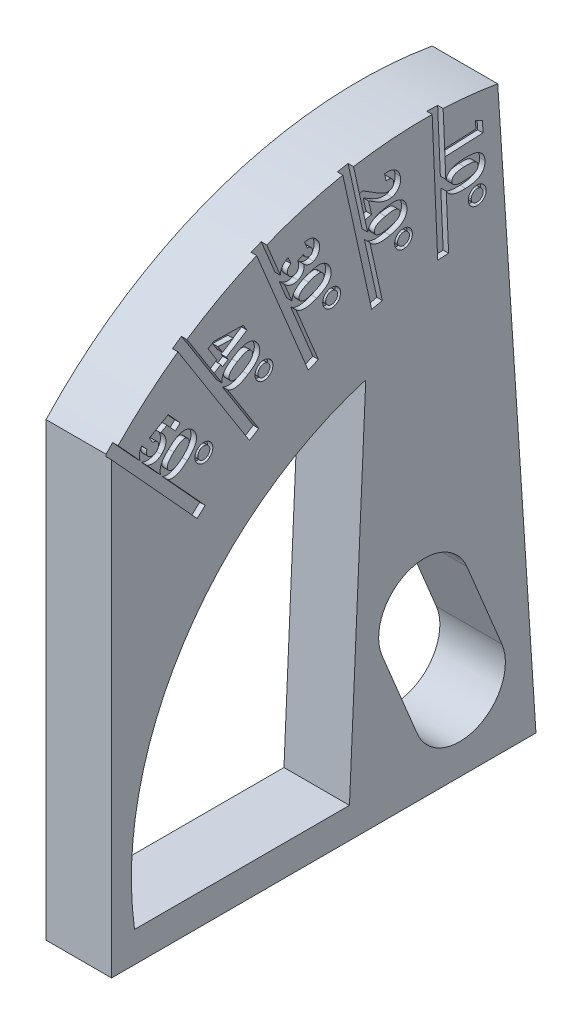
SolidWorks part; units mm, degrees
ref_plane "Front Plane" through (0, 0, 0) normal (0, 0, 1) x (1, 0, 0)
ref_plane "Top Plane" through (0, 0, 0) normal (0, 1, 0) x (1, 0, 0)
ref_plane "Right Plane" through (0, 0, 0) normal (1, 0, 0) x (0, 0, -1)
sketch "Sketch2" plane through (0, 0, 0) normal (1, 0, 0) x (0, 0, -1)
  line L0 (-8.5, 42.0279) -> (-7, 7) construction
  line L1 (0, 0) -> (-14, 0)
  line L5 (-7, 7) -> (-22.9981, 6.3149) construction
  line L6 (-14.5597, 41.2353) -> (-7, 7) construction
  line L7 (-20.3898, 39.4024) -> (-7, 7) construction
  line L8 (0, 0) -> (-3.5, 53.243)
  line L9 (-25.813, 36.585) -> (-7, 7) construction
  line L10 (-30.6646, 32.8687) -> (-7, 7) construction
  line L11 (-13.233, 49.161) -> (-10.0249, 41.3977)
  line L12 (-14, 0) -> (-38.8726, 0)
  line L13 (-38.8726, 0) -> (-38.8726, 41.2968)
  line L14 (-6.9751, 42.658) -> (-10.1831, 50.4213)
  line L15 (-14.0897, 13.1592) -> (-10.8816, 5.396)
  line L16 (-6.3264, 16.3673) -> (-3.1184, 8.604)
  line L17 (-32.1895, 32.2386) -> (-35.3975, 40.0019)
  line L18 (-29.1396, 33.4989) -> (-32.3477, 41.2622)
  line L19 (-17.208, 0) -> (-14.7869, 53.554) construction
  line L20 (-38.8726, 2.8) -> (-17.0815, 2.8)
  line L21 (-30.546, 43.7182) -> (-27.3379, 35.9549)
  line L22 (-27.4961, 44.9785) -> (-24.2881, 37.2152)
  line L23 (-25.1228, 46.5355) -> (-21.9147, 38.7723)
  line L24 (-22.0729, 47.7959) -> (-18.8649, 40.0326)
  line L25 (-19.2927, 48.3684) -> (-16.0847, 40.6051)
  line L26 (-16.2429, 49.6287) -> (-13.0348, 41.8654)
  line L27 (-17.0815, 2.8) -> (-15.5893, 35.8067)
  circle A0 centre (-7, 7) radius 4.2
  circle A2 centre (-8.5, 42.0279) radius 1.65
  circle A3 centre (-7, 7) radius 35.06 construction
  circle A4 centre (-14.5597, 41.2353) radius 1.65
  circle A5 centre (-7, 7) radius 30.06
  circle A6 centre (-7, 7) radius 40.06 construction
  circle A7 centre (-20.3898, 39.4024) radius 1.65
  circle A8 centre (-25.813, 36.585) radius 1.65
  circle A9 centre (-30.6646, 32.8687) radius 1.65
  circle A11 centre (-10.208, 14.7633) radius 4.2
  circle A12 centre (-10.208, 14.7633) radius 35.06 construction
  circle A13 centre (-33.8726, 40.632) radius 1.65
  circle A14 centre (-11.708, 49.7912) radius 1.65
  circle A15 centre (-10.208, 14.7633) radius 36.71
  circle A16 centre (-10.208, 14.7633) radius 33.41
  circle A17 centre (-10.208, 14.7633) radius 39.06
  circle A18 centre (-29.021, 44.3483) radius 1.65
  circle A19 centre (-23.5978, 47.1657) radius 1.65
  circle A20 centre (-17.7678, 48.9985) radius 1.65
  point P7 (-7, 0)
  point P72 (0, 0)
  point P74 (0, 0)
  dimension "D3" = 8.4
  dimension "D5" = 3.3
  dimension "D6" = 70.12
  dimension "D8" = 10
  dimension "D11" = 5
  dimension "D12" = 10
  dimension "D13" = 10
  dimension "D14" = 4
  dimension "D17" = 70.12
  dimension "D15" = 3.0789
  dimension "D18" = 5
  dimension "D19" = 3.3
  dimension "D1" = 5
  dimension "D2" = 7
  dimension "D4" = 7
  dimension "D7" = 1.5
  dimension "D9" = 10
  dimension "D16" = 7
  dimension "D10" = 5
extrude "Boss-Extrude6" add sketch "Sketch2" along normal blind 3 contours L8 A5 L27 L20 L12 L1 A11 L16 A0 L15 | A5 L20 L13 L12 | L8 A17 L13 L20 A5 A20 L26 A4 L25 A19 L24 A7 L23 A18 L22 A8 L21 A13 L18 A9 L17 A14 L14 A2 L11 | A13 | A13 L17 A9 L18 | A9 | A8 | A7 | A4 | A2 | A14 L11 A2 L14 | A20 L25 A4 L26 | A19 L23 A7 L24 | A18 L21 A8 L22 | A18 | A19 | L8 A17 L13 A15 | A16 L17 A13 A15 L13 | A16 A13 L17 | A16 L18 A13 | A18 A15 A13 L18 A16 L21 | A18 L21 A16 | A18 A16 L22 | A19 A15 A18 L22 A16 L23 | A19 L23 A16 | A19 A16 L24 | A20 A15 A19 L24 A16 L25 | A20 L25 A16 | A16 L8 A15 A14 L14 | A16 L14 A14 | A20 L26 A16 L11 A14 A15 | A20 A16 L26 | A16 A14 L11 | A20 | A14 region at (0, 0.522, 7) region at (0, 33.001, 24.3817) region at (0, 1.3473, 37.6924) region at (0, 49.6423, 6.6257) region at (0, 51.7655, 7.5138) region at (0, 48.7084, 10.044) region at (0, 45.6614, 10.0725) region at (0, 37.0768, 37.033) region at (0, 49.7013, 14.6927) region at (0, 42.0279, 8.5) region at (0, 48.3248, 12.6352) region at (0, 36.5524, 32.1158) region at (0, 38.6904, 34.2868) region at (0, 48.3604, 20.7414) region at (0, 48.9985, 17.7678) region at (0, 42.6753, 31.6952) region at (0, 40.632, 33.8726) region at (0, 32.8687, 30.6646) region at (0, 40.2479, 32.1808) region at (0, 45.9955, 26.4644) region at (0, 47.1657, 23.5978) region at (0, 48.1126, 16.0991) region at (0, 47.4238, 18.5791) region at (0, 44.9135, 16.1134) region at (0, 44.3483, 29.021) region at (0, 46.4572, 21.9203) region at (0, 45.4796, 24.2859) region at (0, 41.2353, 14.5597) region at (0, 43.8056, 27.3347) region at (0, 42.5429, 29.5775) region at (0, 40.2871, 27.3091) region at (0, 43.1027, 21.9188) region at (0, 36.585, 25.813) region at (0, 39.4024, 20.3898)
extrude "Boss-Extrude7" add sketch "Sketch2<12>" against normal blind 3 contours L8 A17 L13 A15 | A16 L8 A15 A14 L14 | L8 A16 L14 A2 L11 L26 A4 L25 L24 A7 L23 L22 A8 L21 L18 A9 L17 L13 L20 A5 | L8 A5 L27 L20 L12 L1 A11 L16 A0 L15 | A5 L20 L13 L12 | A16 L17 A13 A15 L13 region at (0, 0.522, 7) region at (0, 33.001, 24.3817) region at (0, 1.3473, 37.6924) region at (0, 49.6423, 6.6257) region at (0, 51.7655, 7.5138) region at (0, 37.0768, 37.033)
sketch "Sketch2<12>" plane through (0, 0, 0) normal (1, 0, 0) x (0, 0, -1) same geometry as "Sketch2"
sketch "Sketch5" plane through (3, 0, 0) normal (1, 0, 0) x (0, 0, -1)
  line L0 (-8.5, 42.0279) -> (-9.0501, 54.8734)
  line L1 (-14.5597, 41.2353) -> (-17.4386, 54.2724)
  line L2 (-20.3898, 39.4024) -> (-25.5288, 51.8384)
  line L3 (-25.813, 36.585) -> (-33.6355, 48.8866)
  line L4 (-30.6646, 32.8687) -> (-40.0326, 43.1093)
  line L5 (-30.6646, 32.8687) -> (-7, 7) construction
  line L6 (-7, 7) -> (-25.813, 36.585) construction
  line L7 (-20.3898, 39.4024) -> (-7, 7) construction
  line L8 (-7, 7) -> (-14.5597, 41.2353) construction
  line L9 (-7, 7) -> (-8.5, 42.0279) construction
  circle A0 centre (-7, 7) radius 35.06 construction
  circle A1 centre (-7, 7) radius 35.06 construction
  point P0 (-30.6646, 32.8687)
  point P2 (-25.813, 36.585)
  point P4 (-20.3898, 39.4024)
  point P6 (-14.5597, 41.2353)
  point P8 (-8.5, 42.0279)
  point P15 (-9.0501, 54.8734)
  point P16 (-17.4386, 54.2724)
  point P17 (-25.5288, 51.8384)
  point P26 (-33.6355, 48.8866)
  point P27 (-40.0326, 43.1093)
extrude "Cut-Extrude-Thin12" cut sketch "Sketch5" against normal blind 0.5 thin thin type mid plane wall 1
sketch "Sketch6" plane through (3, 0, 0) normal (1, 0, 0) x (0, 0, -1)
  text T0 "<b>10°</b>"
  text T1 "<b>20°</b>"
  text T2 "<b>30°</b>"
  text T3 "<b>40°</b>"
  text T4 "<b>50°</b>"
extrude "Cut-Extrude1" cut sketch "Sketch6" against normal blind 0.5
